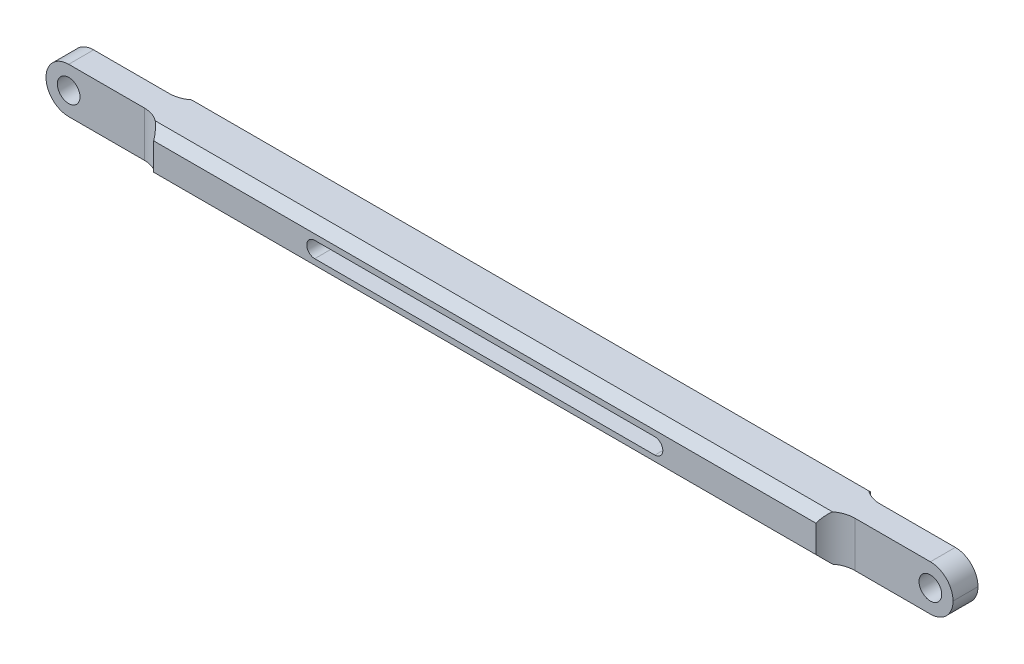
SolidWorks part; units mm, degrees
ref_plane "Front Plane" through (0, 0, 0) normal (0, 0, 1) x (1, 0, 0)
ref_plane "Top Plane" through (0, 0, 0) normal (0, 1, 0) x (1, 0, 0)
ref_plane "Right Plane" through (0, 0, 0) normal (1, 0, 0) x (0, 0, -1)
sketch "Sketch1" plane through (0, 0, 0) normal (0, 0, 1) x (1, 0, 0)
  line L1 (-100, 5) -> (100, 5)
  line L2 (-100, 5) -> (-100, -5)
  line L3 (-100, -5) -> (100, -5)
  line L4 (100, 5) -> (100, -5)
  line L5 (-100, 5) -> (100, -5) construction
  line L6 (-100, -5) -> (100, 5) construction
  point P0 (0, 0)
  dimension "D1" = 10
  dimension "D2" = 200
extrude "Boss-Extrude1" add sketch "Sketch1" along normal mid plane 12
sketch "Sketch2" plane through (0, 0, 0) normal (0, 1, 0) x (1, 0, 0)
  line L0 (0, 0) -> (70.0367, 0) construction
  line L1 (0, 0) -> (0, 13.955) construction
  line L2 (100, -6) -> (100, 6) construction
  line L3 (127, 9.25) -> (73, 9.25)
  line L4 (127, 9.25) -> (127, 2.75)
  line L5 (127, 2.75) -> (73, 2.75)
  line L6 (73, 9.25) -> (73, 2.75)
  line L7 (127, 9.25) -> (73, 2.75) construction
  line L8 (127, 2.75) -> (73, 9.25) construction
  line L9 (127, -2.75) -> (73, -9.25) construction
  line L10 (127, -9.25) -> (73, -2.75) construction
  line L11 (73, -9.25) -> (73, -2.75)
  line L12 (127, -2.75) -> (73, -2.75)
  line L13 (127, -9.25) -> (127, -2.75)
  line L14 (127, -9.25) -> (73, -9.25)
  line L15 (-127, -9.25) -> (-73, -2.75) construction
  line L16 (-127, -2.75) -> (-73, -9.25) construction
  line L17 (-127, 2.75) -> (-73, 9.25) construction
  line L18 (-127, 9.25) -> (-73, 2.75) construction
  line L19 (-127, -9.25) -> (-73, -9.25)
  line L20 (-127, -9.25) -> (-127, -2.75)
  line L21 (-127, -2.75) -> (-73, -2.75)
  line L22 (-73, -9.25) -> (-73, -2.75)
  line L23 (-73, 9.25) -> (-73, 2.75)
  line L24 (-127, 2.75) -> (-73, 2.75)
  line L25 (-127, 9.25) -> (-127, 2.75)
  line L26 (-127, 9.25) -> (-73, 9.25)
  point P3 (100, 6)
  point P16 (100, -6)
  point P25 (-100, -6)
  point P26 (-100, 6)
  dimension "D1" = 27
  dimension "D2" = 2.75
extrude "Cut-Extrude1" cut sketch "Sketch2" against normal mid plane 31
fillet "Fillet1" radius 6 4 edges at (73, 0, -2.75) (73, 0, 2.75) (-73, 0, -2.75) (-73, 0, 2.75)
fillet "Fillet2" radius 5 4 edges at (-100, -5, 0) (-100, 5, 0) (100, -5, 0) (100, 5, 0)
chamfer "Chamfer1" distance 2 angle 45 4 edges at (0, 5, 6) (0, -5, 6) (0, 5, -6) (0, -5, -6)
sketch "Sketch3" plane through (0, 0, -6) normal (0, 0, -1) x (-1, 0, 0)
  line L0 (-37.5, 0) -> (37.5, 0) construction
  line L1 (-37.5, 1.75) -> (37.5, 1.75)
  line L2 (-37.5, -1.75) -> (37.5, -1.75)
  arc A0 (-37.5, 1.75) -> (-37.5, -1.75) centre (-37.5, 0) ccw
  arc A1 (37.5, -1.75) -> (37.5, 1.75) centre (37.5, 0) ccw
  point P2 (0, 0)
  dimension "D2" = 1.75
  dimension "D1" = 75
extrude "Cut-Extrude2" cut sketch "Sketch3" against normal blind 31
sketch "Sketch4" plane through (0, 0, -2.75) normal (0, 0, -1) x (-1, 0, 0)
  circle A0 centre (95, 0) radius 2.5
  circle A1 centre (-95, 0) radius 2.5
  dimension "D1" = 5
extrude "Cut-Extrude3" cut sketch "Sketch4" against normal blind 31
